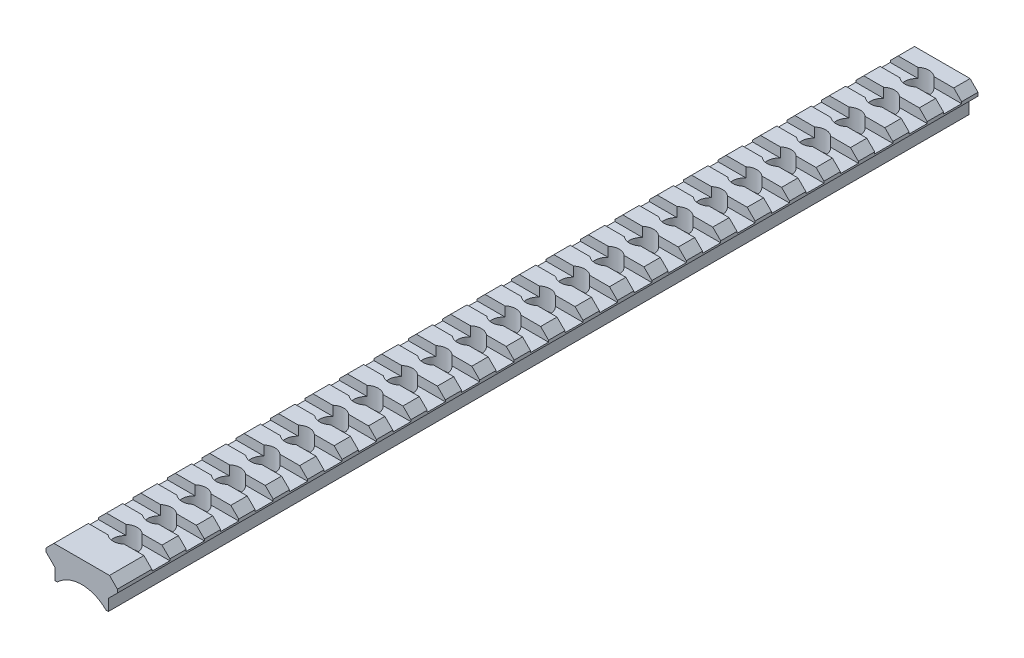
SolidWorks part; units mm, degrees
ref_plane "Płaszczyzna przednia" through (0, 0, 0) normal (0, 0, 1) x (1, 0, 0)
ref_plane "Płaszczyzna górna" through (0, 0, 0) normal (0, 1, 0) x (1, 0, 0)
ref_plane "Płaszczyzna prawa" through (0, 0, 0) normal (1, 0, 0) x (0, 0, -1)
sketch "Szkic1" plane through (0, 0, 0) normal (0, 0, 1) x (1, 0, 0)
  line L0 (2.8, 2.8) -> (0, 0)
  line L5 (3.12, -3.12) -> (18.62, -3.12) construction
  line L6 (1.37, 1.37) -> (20.37, 1.37) construction
  line L7 (0, 0) -> (3.12, -3.12)
  line L8 (18.94, 2.8) -> (21.74, 0)
  line L9 (21.74, 0) -> (18.62, -3.12)
  line L14 (2.8, 2.8) -> (18.94, 2.8)
  line L15 (21.74, 0) -> (0, 0) construction
  line L16 (1.37, 1.37) -> (1.37, -1.37) construction
  line L17 (1.37, -1.37) -> (20.37, -1.37) construction
  line L18 (20.37, 1.37) -> (20.37, -1.37) construction
  line L24 (3.12, -3.12) -> (3.12, -7.2)
  line L25 (3.12, -7.2) -> (18.62, -7.2)
  line L26 (18.62, -7.2) -> (18.62, -3.12)
  dimension "D1" = 19
  dimension "D2" = 45
  dimension "D3" = 15.5
  dimension "D4" = 10
  dimension "D5" = 4.17
  dimension "D6" = 2.74
extrude "Dodanie-wyciągnięcie2" add sketch "Szkic1" along normal blind 250
sketch "Szkic2" plane through (0, 2.8, 0) normal (0, 1, 0) x (1, 0, 0)
  line L0 (0, -14.75) -> (0, -20)
  line L6 (0, -250) -> (0, 0) construction
  line L7 (0, -4.75) -> (21.74, -4.75)
  line L8 (0, -4.75) -> (0, -10)
  line L9 (0, -10) -> (21.74, -10)
  line L10 (21.74, -4.75) -> (21.74, -10)
  line L11 (21.74, -250) -> (21.74, 0) construction
  line L12 (0, -14.75) -> (21.74, -14.75)
  line L14 (21.74, -14.75) -> (21.74, -20)
  line L24 (0, -20) -> (21.74, -20)
  line L26 (0, -24.75) -> (0, -30)
  line L28 (0, -24.75) -> (21.74, -24.75)
  line L30 (21.74, -24.75) -> (21.74, -30)
  line L32 (0, -30) -> (21.74, -30)
  line L34 (0, -34.75) -> (0, -40)
  line L35 (0, -34.75) -> (21.74, -34.75)
  line L60 (21.74, -34.75) -> (21.74, -40)
  line L61 (0, -40) -> (21.74, -40)
  line L62 (0, -44.75) -> (0, -50)
  line L63 (0, -44.75) -> (21.74, -44.75)
  line L64 (21.74, -44.75) -> (21.74, -50)
  line L65 (0, -50) -> (21.74, -50)
  line L66 (0, -54.75) -> (0, -60)
  line L67 (0, -54.75) -> (21.74, -54.75)
  line L68 (21.74, -54.75) -> (21.74, -60)
  line L69 (0, -60) -> (21.74, -60)
  line L70 (0, -64.75) -> (0, -70)
  line L71 (0, -64.75) -> (21.74, -64.75)
  line L72 (21.74, -64.75) -> (21.74, -70)
  line L73 (0, -70) -> (21.74, -70)
  line L74 (0, -74.75) -> (0, -80)
  line L75 (0, -74.75) -> (21.74, -74.75)
  line L76 (21.74, -74.75) -> (21.74, -80)
  line L77 (0, -80) -> (21.74, -80)
  line L78 (0, -84.75) -> (0, -90)
  line L79 (0, -84.75) -> (21.74, -84.75)
  line L80 (21.74, -84.75) -> (21.74, -90)
  line L81 (0, -90) -> (21.74, -90)
  line L82 (0, -94.75) -> (0, -100)
  line L83 (0, -94.75) -> (21.74, -94.75)
  line L84 (21.74, -94.75) -> (21.74, -100)
  line L85 (0, -100) -> (21.74, -100)
  line L86 (0, -104.75) -> (0, -110)
  line L87 (0, -104.75) -> (21.74, -104.75)
  line L88 (21.74, -104.75) -> (21.74, -110)
  line L89 (0, -110) -> (21.74, -110)
  line L90 (0, -114.75) -> (0, -120)
  line L91 (0, -114.75) -> (21.74, -114.75)
  line L92 (21.74, -114.75) -> (21.74, -120)
  line L93 (0, -120) -> (21.74, -120)
  line L94 (0, -124.75) -> (0, -130)
  line L95 (0, -124.75) -> (21.74, -124.75)
  line L96 (21.74, -124.75) -> (21.74, -130)
  line L97 (0, -130) -> (21.74, -130)
  line L98 (0, -134.75) -> (0, -140)
  line L99 (0, -134.75) -> (21.74, -134.75)
  line L100 (21.74, -134.75) -> (21.74, -140)
  line L101 (0, -140) -> (21.74, -140)
  line L102 (0, -144.75) -> (0, -150)
  line L103 (0, -144.75) -> (21.74, -144.75)
  line L104 (21.74, -144.75) -> (21.74, -150)
  line L105 (0, -150) -> (21.74, -150)
  line L106 (0, -154.75) -> (0, -160)
  line L107 (0, -154.75) -> (21.74, -154.75)
  line L108 (21.74, -154.75) -> (21.74, -160)
  line L109 (0, -160) -> (21.74, -160)
  line L110 (0, -164.75) -> (0, -170)
  line L111 (0, -164.75) -> (21.74, -164.75)
  line L112 (21.74, -164.75) -> (21.74, -170)
  line L113 (0, -170) -> (21.74, -170)
  line L114 (0, -174.75) -> (0, -180)
  line L115 (0, -174.75) -> (21.74, -174.75)
  line L116 (21.74, -174.75) -> (21.74, -180)
  line L117 (0, -180) -> (21.74, -180)
  line L118 (0, -184.75) -> (0, -190)
  line L119 (0, -184.75) -> (21.74, -184.75)
  line L120 (21.74, -184.75) -> (21.74, -190)
  line L121 (0, -190) -> (21.74, -190)
  line L122 (0, -194.75) -> (0, -200)
  line L123 (0, -194.75) -> (21.74, -194.75)
  line L124 (21.74, -194.75) -> (21.74, -200)
  line L125 (0, -200) -> (21.74, -200)
  line L126 (0, -204.75) -> (0, -210)
  line L127 (0, -204.75) -> (21.74, -204.75)
  line L128 (21.74, -204.75) -> (21.74, -210)
  line L129 (0, -210) -> (21.74, -210)
  line L130 (0, -214.75) -> (0, -220)
  line L131 (0, -214.75) -> (21.74, -214.75)
  line L132 (21.74, -214.75) -> (21.74, -220)
  line L133 (0, -220) -> (21.74, -220)
  line L134 (0, -224.75) -> (0, -230)
  line L135 (0, -224.75) -> (21.74, -224.75)
  line L136 (21.74, -224.75) -> (21.74, -230)
  line L137 (0, -230) -> (21.74, -230)
  line L138 (0, -234.75) -> (0, -240)
  line L139 (0, -234.75) -> (21.74, -234.75)
  line L140 (21.74, -234.75) -> (21.74, -240)
  line L141 (0, -240) -> (21.74, -240)
  dimension "D1" = 4.75
  dimension "D2" = 5.25
  dimension "D3" = 24
  dimension "D4" = 10
extrude "Wytnij-wyciągnięcie2" cut sketch "Szkic2" against normal blind 2.8
sketch "Szkic3" plane through (0, 0, 0) normal (0, 1, 0) x (1, 0, 0)
  line L0 (10.87, -7.375) -> (10.87, 0) construction
  line L1 (18.94, 0) -> (2.8, 0) construction
  line L2 (21.74, -7.375) -> (10.87, -7.375) construction
  line L3 (21.74, -10) -> (21.74, -4.75) construction
  circle A0 centre (10.87, -7.375) radius 1.75
  circle A9 centre (10.87, -17.375) radius 1.75
  circle A10 centre (10.87, -27.375) radius 1.75
  circle A11 centre (10.87, -37.375) radius 1.75
  circle A12 centre (10.87, -47.375) radius 1.75
  circle A13 centre (10.87, -57.375) radius 1.75
  circle A14 centre (10.87, -67.375) radius 1.75
  circle A15 centre (10.87, -77.375) radius 1.75
  circle A16 centre (10.87, -87.375) radius 1.75
  circle A17 centre (10.87, -97.375) radius 1.75
  circle A18 centre (10.87, -107.375) radius 1.75
  circle A19 centre (10.87, -117.375) radius 1.75
  circle A20 centre (10.87, -127.375) radius 1.75
  circle A21 centre (10.87, -137.375) radius 1.75
  circle A22 centre (10.87, -147.375) radius 1.75
  circle A23 centre (10.87, -157.375) radius 1.75
  circle A24 centre (10.87, -167.375) radius 1.75
  circle A25 centre (10.87, -177.375) radius 1.75
  circle A26 centre (10.87, -187.375) radius 1.75
  circle A27 centre (10.87, -197.375) radius 1.75
  circle A28 centre (10.87, -207.375) radius 1.75
  circle A29 centre (10.87, -217.375) radius 1.75
  circle A30 centre (10.87, -227.375) radius 1.75
  circle A31 centre (10.87, -237.375) radius 1.75
  point P23 (10.87, 0)
  dimension "D2" = 3.5
  dimension "D4" = 10
  dimension "D3" = 24
other "Wyrównaj grupę1"
extrude "Wytnij-wyciągnięcie3" cut sketch "Szkic3" against normal through all
sketch "Szkic4" plane through (0, 0, -1.86) normal (0, -1, 0) x (1, 0, 0)
  circle A33 centre (10.87, 9.235) radius 3.5
  circle A34 centre (10.87, 19.235) radius 3.5
  circle A35 centre (10.87, 29.235) radius 3.5
  circle A36 centre (10.87, 39.235) radius 3.5
  circle A37 centre (10.87, 49.235) radius 3.5
  circle A38 centre (10.87, 59.235) radius 3.5
  circle A39 centre (10.87, 69.235) radius 3.5
  circle A40 centre (10.87, 79.235) radius 3.5
  circle A41 centre (10.87, 89.235) radius 3.5
  circle A42 centre (10.87, 99.235) radius 3.5
  circle A43 centre (10.87, 109.235) radius 3.5
  circle A44 centre (10.87, 119.235) radius 3.5
  circle A45 centre (10.87, 129.235) radius 3.5
  circle A46 centre (10.87, 139.235) radius 3.5
  circle A47 centre (10.87, 149.235) radius 3.5
  circle A48 centre (10.87, 159.235) radius 3.5
  circle A49 centre (10.87, 169.235) radius 3.5
  circle A50 centre (10.87, 179.235) radius 3.5
  circle A51 centre (10.87, 189.235) radius 3.5
  circle A52 centre (10.87, 199.235) radius 3.5
  circle A53 centre (10.87, 209.235) radius 3.5
  circle A54 centre (10.87, 219.235) radius 3.5
  circle A55 centre (10.87, 229.235) radius 3.5
  circle A56 centre (10.87, 239.235) radius 3.5
  dimension "D1" = 7
  dimension "D2" = 24
extrude "Wytnij-wyciągnięcie4" cut sketch "Szkic4" along normal blind 3.2 and the other way through all
sketch "Sketch1" plane through (0, 0, 250) normal (0, 0, 1) x (1, 0, 0)
  line L0 (10.87, -7.2) -> (10.87, 10.5404) construction
  line L1 (0.5, 0.5) -> (0.5, -0.5)
  line L3 (3.12, -7.2) -> (18.62, -7.2) construction
  line L8 (18.94, 2.8) -> (2.8, 2.8)
  line L9 (2.8, 2.8) -> (0, 0)
  line L10 (0, 0) -> (3.12, -3.12)
  line L11 (3.12, -3.12) -> (3.12, -7.2)
  line L12 (3.12, -7.2) -> (18.62, -7.2)
  line L14 (18.62, -3.12) -> (21.74, 0)
  line L15 (21.74, 0) -> (18.94, 2.8)
  line L17 (0.5, 0.5) -> (0, 0)
  line L18 (0, 0) -> (0.5, -0.5)
  line L29 (21.24, 0.5) -> (21.24, -0.5)
  line L30 (21.74, 0) -> (21.24, -0.5)
  line L31 (21.24, 0.5) -> (21.74, 0)
  line L32 (18.62, -7.2) -> (18.62, -3.12)
  dimension "D1" = 0
extrude "Cut-Extrude1" cut sketch "Sketch1" against normal through all
sketch "Sketch2" plane through (0, 0, 0) normal (0, 0, -1) x (-1, 0, 0)
  circle A0 centre (-10.87, -13.5196) radius 10
  dimension "D1" = 20
extrude "Cut-Extrude2" cut sketch "Sketch2" against normal through all
sketch "Sketch3" plane through (0, 0, 250) normal (0, 0, 1) x (1, 0, 0)
  line L0 (18.62, -7.2) -> (18.62, -3.12) construction
  line L1 (3.12, -7.2) -> (18.62, -7.2)
  line L2 (3.12, -7.2) -> (3.12, -6.45)
  line L3 (3.12, -6.45) -> (18.62, -6.45)
  line L4 (18.62, -7.2) -> (18.62, -6.45)
  dimension "D1" = 0.75
extrude "Cut-Extrude3" cut sketch "Sketch3" against normal through all
